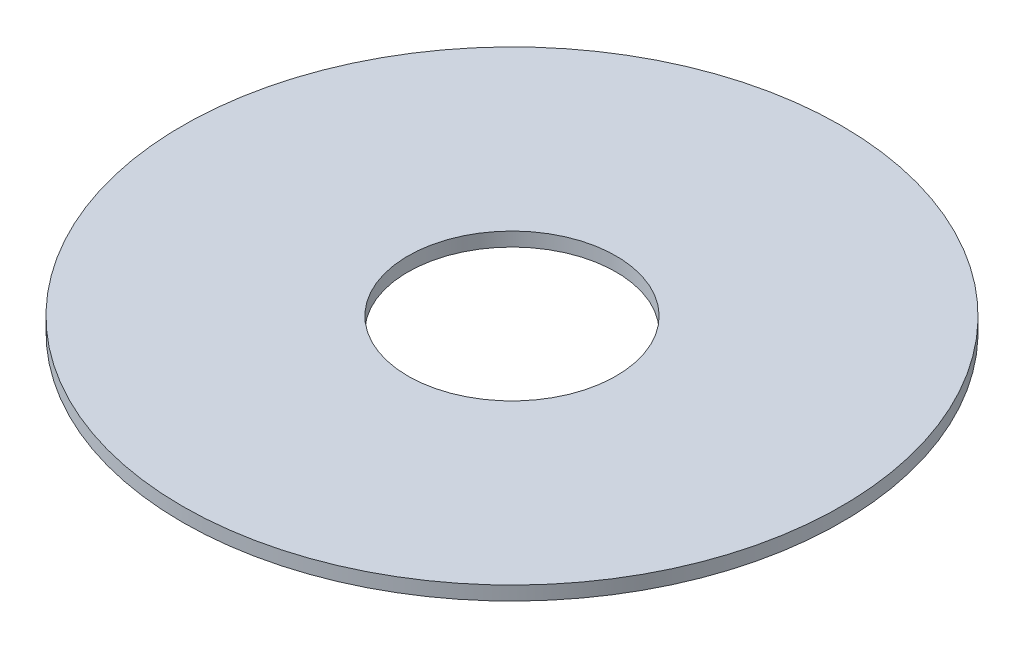
SolidWorks part; units mm, degrees
ref_plane "Front Plane" through (0, 0, 0) normal (0, 0, 1) x (1, 0, 0)
ref_plane "Top Plane" through (0, 0, 0) normal (0, 1, 0) x (1, 0, 0)
ref_plane "Right Plane" through (0, 0, 0) normal (1, 0, 0) x (0, 0, -1)
sketch "Sketch1" plane through (0, 0, 0) normal (0, 1, 0) x (1, 0, 0)
  circle A0 centre (0, 0) radius 95
  dimension "FLANGE_OD" = 190
extrude "Boss-Extrude1" add sketch "Sketch1" along normal blind 4
sketch "Sketch2" plane through (0, 0, 0) normal (0, 1, 0) x (1, 0, 0)
  circle A0 centre (0, 0) radius 30
  dimension "BORE_D" = 60
extrude "Cut-Extrude1" cut sketch "Sketch2" along normal through all
sketch "Sketch3" plane through (0, 4, 0) normal (0, 1, 0) x (1, 0, 0)
  circle A0 centre (0, 0) radius 26.6027 construction
  circle A1 centre (-26.6027, 0) radius 3.207
  dimension "BOLT_D" = 6.4139
  dimension "BOLT_PCD" = 53.2053
extrude "Cut-Extrude2" cut sketch "Sketch3" against normal blind 3.7673 rebuild error yes
pattern_circular "CirPattern1" count 3 over 360 rebuild error yes
